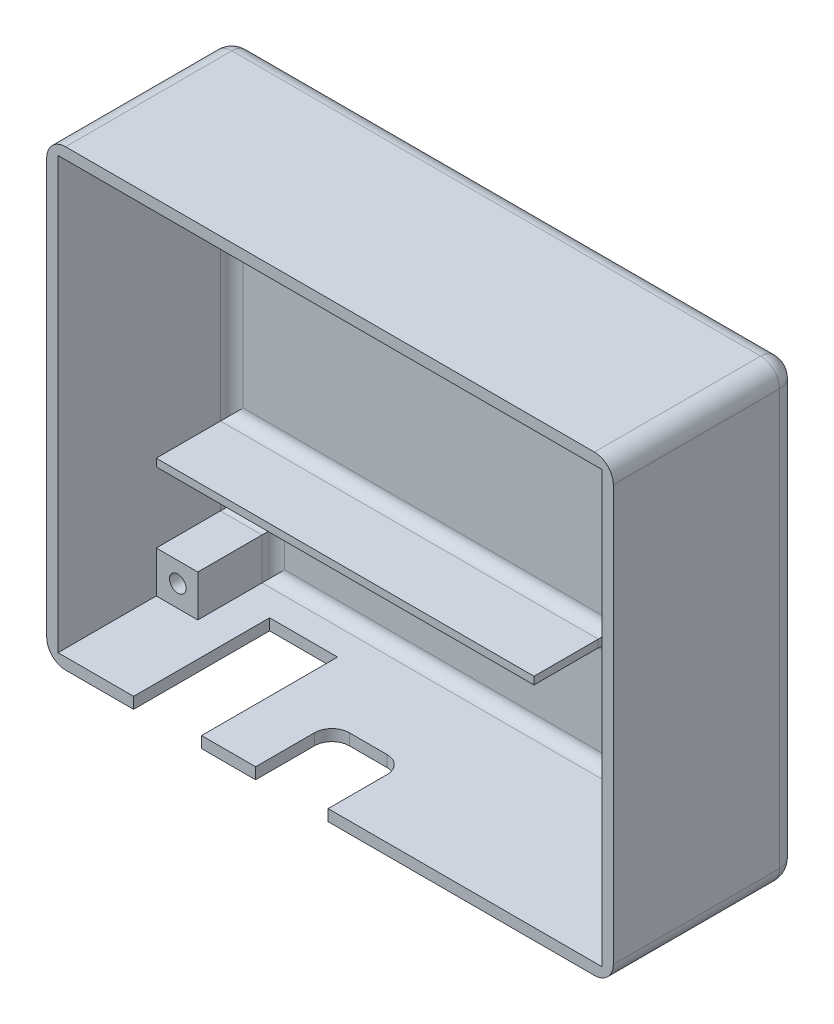
SolidWorks part; units mm, degrees
ref_plane "Front Plane" through (0, 0, 0) normal (0, 0, 1) x (1, 0, 0)
ref_plane "Top Plane" through (0, 0, 0) normal (0, 1, 0) x (1, 0, 0)
ref_plane "Right Plane" through (0, 0, 0) normal (1, 0, 0) x (0, 0, -1)
sketch "Sketch2" plane through (0, 0, 0) normal (0, 0, 1) x (1, 0, 0)
  line L1 (0, 0) -> (75, 0)
  line L2 (0, 0) -> (0, 60)
  line L3 (0, 60) -> (75, 60)
  line L4 (75, 0) -> (75, 60)
  dimension "D1" = 75
  dimension "D2" = 60
extrude "Body creation" add sketch "Sketch2" along normal blind 24.5
shell "Thikness of walls" thickness 1.5 removed face at (37.5, 30, 24.5)
ref_plane "Plane1" through (0, 30, 0) normal (0, -1, 0) x (-1, 0, 0)
sketch "Sketch6" plane through (0, 0, 1.5) normal (0, 0, 1) x (1, 0, 0)
  line L1 (1.5, 58.5) -> (7, 58.5)
  line L2 (1.5, 58.5) -> (1.5, 53)
  line L3 (1.5, 53) -> (7, 53)
  line L4 (7, 58.5) -> (7, 53)
  line L5 (73.5, 58.5) -> (68, 58.5)
  line L6 (73.5, 58.5) -> (73.5, 53)
  line L7 (73.5, 53) -> (68, 53)
  line L8 (68, 58.5) -> (68, 53)
  dimension "D1" = 5.5
extrude "Corner rect." add sketch "Sketch6" along normal blind 10
sketch "Sketch8" plane through (0, 0, 24.5) normal (0, 0, 1) x (1, 0, 0)
  line L0 (4.35, 55.65) -> (4.35, 53) construction
  line L1 (1.5, 53) -> (7, 53) construction
  line L2 (7, 55.65) -> (4.35, 55.65) construction
  line L3 (7, 53) -> (7, 58.5) construction
  line L4 (68, 55.65) -> (70.65, 55.65) construction
  line L7 (70.65, 55.65) -> (70.65, 53) construction
  line L9 (68, 58.5) -> (68, 53) construction
  line L10 (68, 53) -> (73.5, 53) construction
  circle A0 centre (4.35, 55.65) radius 1.1
  circle A1 centre (70.65, 55.65) radius 1.1
  dimension "D1" = 2.2
  dimension "D2" = 2.65
  dimension "D3" = 2.65
extrude "Screw hole" cut sketch "Sketch8" against normal up to surface (24.5 mm away) up to face at (37.5, 30, 0)
sketch "Sketch10" plane through (0, 0, 0) normal (0, 0, -1) x (-1, 0, 0)
  circle A0 centre (-70.65, 55.65) radius 1.85
  circle A1 centre (-4.35, 55.65) radius 1.85
  dimension "D1" = 3.7
extrude "Screw head" cut sketch "Sketch10" against normal blind 4
mirror "Mirror to other side" about plane through (0, 30, 0) normal (0, -1, 0) of "Screw head", "Corner rect.", "Screw hole"
sketch "Sketch5" plane through (0, 0, 0) normal (0, -1, 0) x (1, 0, 0)
  line L0 (32.45, 16.7) -> (32.45, 24.5) construction
  line L1 (20.5, 24.5) -> (11.5, 24.5)
  line L2 (20.5, 24.5) -> (20.5, 6.5)
  line L3 (20.5, 6.5) -> (11.5, 6.5)
  line L4 (11.5, 24.5) -> (11.5, 6.5)
  line L5 (0, 24.5) -> (0, 0) construction
  line L6 (29.95, 16.7) -> (34.95, 16.7) construction
  line L7 (16, 24.5) -> (16, 6.5) construction
  line L10 (29.95, 14.4) -> (34.95, 14.4)
  line L13 (27.65, 16.7) -> (27.65, 24.5)
  line L14 (37.25, 16.7) -> (37.25, 24.5)
  line L15 (27.65, 24.5) -> (37.25, 24.5)
  line L16 (0, 24.5) -> (75, 24.5) construction
  arc A0 (27.65, 16.7) -> (29.95, 14.4) centre (29.95, 16.7) ccw
  arc A1 (34.95, 14.4) -> (37.25, 16.7) centre (34.95, 16.7) ccw
  dimension "D6" = 7.8
  dimension "D8" = 2.3
  dimension "D1" = 18
  dimension "D2" = 9
  dimension "D3" = 10.1
  dimension "D4" = 16
  dimension "D5" = 5
  dimension "D7" = 11.95
extrude "Ports cut out" cut sketch "Sketch5" against normal up to surface (1.5 mm away) up to face at (37.5, 1.5, 12.25)
sketch "Sketch11" plane through (0, 0, 1.5) normal (0, 0, 1) x (1, 0, 0)
  line L0 (1.5, 53) -> (1.5, 7) construction
  line L1 (7, 53) -> (51.5, 53)
  line L3 (1.5, 17.3) -> (51.5, 17.3)
  line L5 (7, 54) -> (51.5, 54)
  line L6 (1.5, 16.3) -> (51.5, 16.3)
  line L7 (51.5, 17.3) -> (51.5, 16.3)
  line L8 (51.5, 54) -> (51.5, 53)
  line L9 (7, 54) -> (7, 53)
  line L10 (1.5, 17.3) -> (1.5, 16.3)
  line L11 (1.5, 58.5) -> (1.5, 1.5) construction
  line L12 (68, 58.5) -> (66.75, 58.5)
  line L13 (68, 58.5) -> (68, 36)
  line L14 (68, 36) -> (66.75, 36)
  line L15 (66.75, 58.5) -> (66.75, 36)
  line L16 (68, 58.5) -> (68, 53) construction
  line L18 (68, 58.5) -> (7, 58.5) construction
  dimension "D1" = 35.7
  dimension "D2" = 50
  dimension "D5" = 65.25
  dimension "D6" = 22.5
  dimension "D3" = 1
  dimension "D4" = 1
extrude "Battery Placement" add sketch "Sketch11" along normal blind 10
fillet "Fillet1" radius 1.5 20 edges at (1.5, 11.65, 1.5) (7, 56.25, 1.5) (29.25, 54, 1.5) (26.5, 16.3, 1.5) (1.5, 35.15, 1.5) (26.5, 53, 1.5) (51.5, 53.5, 1.5) (36.875, 58.5, 1.5) (70.75, 53, 1.5) (73.5, 30, 1.5) (70.75, 7, 1.5) (68, 4.25, 1.5) (37.5, 1.5, 1.5) (7, 4.25, 1.5) (4.25, 7, 1.5) (51.5, 16.8, 1.5) (26.5, 17.3, 1.5) (66.75, 47.25, 1.5) (67.375, 36, 1.5) (68, 44.5, 1.5)
fillet "Fillet2" radius 2.5 8 edges at (0, 60, 12.25) (75, 60, 12.25) (75, 0, 12.25) (0, 0, 12.25) (37.5, 60, 0) (75, 30, 0) (37.5, 0, 0) (0, 30, 0)
sketch "Sketch13" plane through (0, 0, 0) normal (0, 0, -1) x (-1, 0, 0)
  line L0 (-37.5, 50) -> (-37.5, 57.5) construction
  line L1 (-62.5, 50) -> (-12.5, 50)
  line L2 (-62.5, 50) -> (-62.5, 10)
  line L3 (-62.5, 10) -> (-12.5, 10)
  line L4 (-12.5, 50) -> (-12.5, 10)
  line L5 (-4.35, 57.5) -> (-70.65, 57.5) construction
  line L6 (-62.5, 30) -> (-72.5, 30) construction
  line L7 (-72.5, 55.65) -> (-72.5, 4.35) construction
  dimension "D1" = 50
  dimension "D2" = 40
extrude "Cut-Extrude1" cut sketch "Sketch13" against normal blind 1
